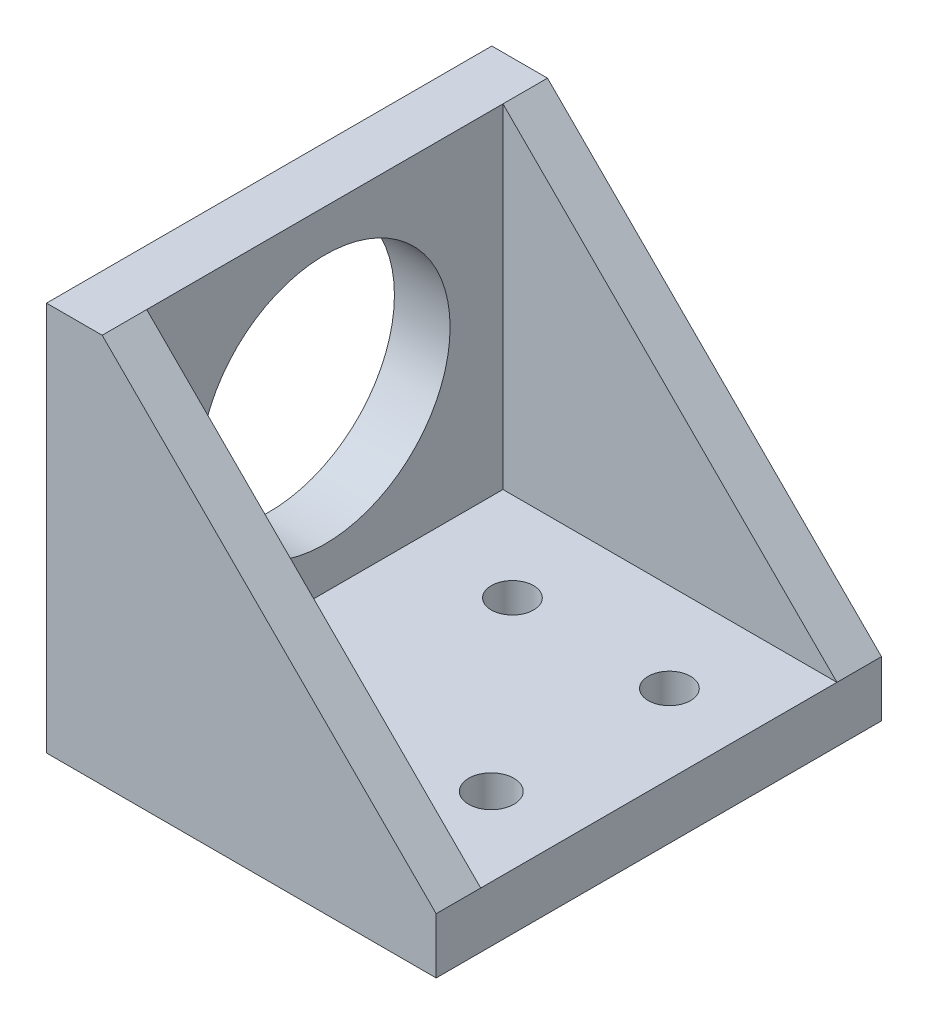
SolidWorks part; units mm, degrees
ref_plane "Front Plane" through (0, 0, 0) normal (0, 0, 1) x (1, 0, 0)
ref_plane "Top Plane" through (0, 0, 0) normal (0, 1, 0) x (1, 0, 0)
ref_plane "Right Plane" through (0, 0, 0) normal (1, 0, 0) x (0, 0, -1)
sketch "Sketch1" plane through (0, 0, 0) normal (1, 0, 0) x (0, 0, -1)
  line L5 (25.4, 19.05) -> (-25.4, 19.05)
  line L6 (25.4, 19.05) -> (25.4, -19.05)
  line L7 (25.4, -19.05) -> (-25.4, -19.05)
  line L8 (-25.4, 19.05) -> (-25.4, -19.05)
  line L9 (25.4, 19.05) -> (-25.4, -19.05) construction
  line L10 (25.4, -19.05) -> (-25.4, 19.05) construction
  line L11 (-25.4, -19.05) -> (25.4, -19.05)
  line L12 (-25.4, -19.05) -> (-25.4, -25.4)
  line L13 (-25.4, -25.4) -> (25.4, -25.4)
  line L14 (25.4, -19.05) -> (25.4, -25.4)
  circle A2 centre (0, 0) radius 14.2875
  dimension "D1" = 28.575
  dimension "D2" = 50.8
  dimension "D3" = 38.1
  dimension "D4" = 6.35
extrude "Boss-Extrude1" add sketch "Sketch1" along normal blind 38.1 contours L14 L7 L12 L13 region at (0, -22.225, 0)
extrude "Boss-Extrude2" add sketch "Sketch1<3>" against normal blind 6.35 separate body contours L5 L8 L7 L6 A2 region at (0, 0, -24.765)
sketch "Sketch1<3>" plane through (0, 0, 0) normal (1, 0, 0) x (0, 0, -1) same geometry as "Sketch1"
sketch "Sketch3" plane through (0, -19.05, 0) normal (0, -1, 0) x (1, 0, 0)
  line L1 (-6.35, -25.4) -> (0, -25.4)
  line L2 (-6.35, -25.4) -> (-6.35, 25.4)
  line L3 (-6.35, 25.4) -> (0, 25.4)
  line L4 (0, -25.4) -> (0, 25.4)
extrude "Boss-Extrude3" add sketch "Sketch3" along normal blind 6.35 contours L2 L1 L4 L3
sketch "Sketch4" plane through (0, 0, 25.4) normal (0, 0, 1) x (1, 0, 0)
  line L0 (0, 19.05) -> (38.1, -19.05)
  line L1 (38.1, -19.05) -> (0, -19.05)
  line L2 (0, -19.05) -> (0, 19.05)
extrude "Boss-Extrude4" add sketch "Sketch4" against normal blind 5.08 contours L2 L0 L1
sketch "Sketch5" plane through (0, 0, -25.4) normal (0, 0, -1) x (-1, 0, 0)
  line L0 (0, 19.05) -> (-38.1, -19.05)
  line L1 (-38.1, -19.05) -> (0, -19.05)
  line L2 (0, -19.05) -> (0, 19.05)
extrude "Boss-Extrude5" add sketch "Sketch5" against normal blind 5.08
sketch "Sketch6" plane through (0, -19.05, 0) normal (0, 1, 0) x (1, 0, 0)
  line L2 (38.1, 20.32) -> (38.1, -20.32) construction
  line L3 (38.1, -20.32) -> (0, -20.32) construction
  line L4 (38.1, 20.32) -> (0, 20.32) construction
  circle A0 centre (11.2395, 10.16) radius 2.413
  circle A1 centre (29.1465, 10.16) radius 2.413
  circle A2 centre (11.2395, -10.16) radius 2.413
  circle A3 centre (29.1465, -10.16) radius 2.5797
  dimension "D1" = 4.826
  dimension "D2" = 4.826
  dimension "D3" = 4.826
  dimension "D4" = 5.1594
  dimension "D5" = 8.9535
  dimension "D6" = 26.8605
  dimension "D7" = 8.9535
  dimension "D9" = 10.16
  dimension "D10" = 10.16
  dimension "D11" = 10.16
  dimension "D12" = 10.16
  dimension "D8" = 26.8605
extrude "Cut-Extrude1" cut sketch "Sketch6" against normal through all contours A2 | A3 | A1 | A0 region at (11.2395, -19.05, 10.16) region at (29.1465, -19.05, 10.16)
